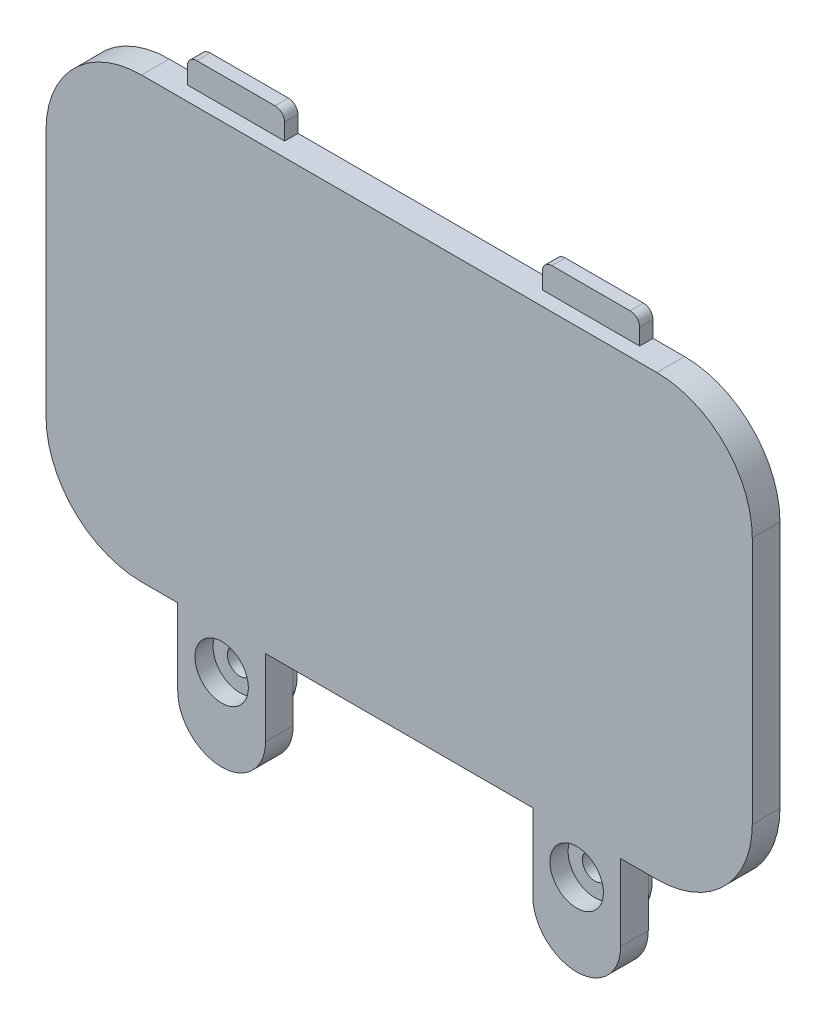
SolidWorks part; units mm, degrees
ref_plane "Plan de face" through (0, 0, 0) normal (0, 0, 1) x (1, 0, 0)
ref_plane "Plan de dessus" through (0, 0, 0) normal (0, 1, 0) x (1, 0, 0)
ref_plane "Plan de droite" through (0, 0, 0) normal (1, 0, 0) x (0, 0, -1)
sketch "Esquisse1" plane through (0, 0, 0) normal (0, 0, 1) x (1, 0, 0)
  line L3 (-14, -15.0013) -> (14, -15.0013) construction
  line L4 (23.2, -15.0013) -> (27, -15.0013) construction
  line L5 (37, -5.0013) -> (37, 20.9987) construction
  line L6 (27, 30.9987) -> (-27, 30.9987) construction
  line L7 (-37, 20.9987) -> (-37, -5.0013) construction
  line L8 (-27, -15.0013) -> (-23.2, -15.0013) construction
  line L10 (23.2, -23.0013) -> (23.2, -15.0013)
  line L11 (14, -15.0013) -> (14, -23.0013)
  line L12 (-14, -23.0013) -> (-14, -15.0013)
  line L13 (-14, -15.0013) -> (14, -15.0013)
  line L14 (23.2, -15.0013) -> (27, -15.0013)
  line L15 (37, -5.0013) -> (37, 20.9987)
  line L16 (27, 30.9987) -> (-27, 30.9987)
  line L17 (-37, 20.9987) -> (-37, -5.0013)
  line L18 (-27, -15.0013) -> (-23.2, -15.0013)
  line L19 (-23.2, -15.0013) -> (-23.2, -23.0013)
  arc A1 (27, -15.0013) -> (37, -5.0013) centre (27, -5.0013) ccw construction
  arc A2 (37, 20.9987) -> (27, 30.9987) centre (27, 20.9987) ccw construction
  arc A3 (-27, 30.9987) -> (-37, 20.9987) centre (-27, 20.9987) ccw construction
  arc A4 (-37, -5.0013) -> (-27, -15.0013) centre (-27, -5.0013) ccw construction
  arc A6 (14, -23.0013) -> (23.2, -23.0013) centre (18.6, -23.0013) ccw
  arc A7 (27, -15.0013) -> (37, -5.0013) centre (27, -5.0013) ccw
  arc A8 (37, 20.9987) -> (27, 30.9987) centre (27, 20.9987) ccw
  arc A9 (-27, 30.9987) -> (-37, 20.9987) centre (-27, 20.9987) ccw
  arc A10 (-37, -5.0013) -> (-27, -15.0013) centre (-27, -5.0013) ccw
  arc A11 (-23.2, -23.0013) -> (-14, -23.0013) centre (-18.6, -23.0013) ccw
  dimension "D2" = 4.6
  dimension "D3" = 4.6
  dimension "D1" = 8
extrude "Extrusion1" add sketch "Esquisse1" against normal blind 2.9
sketch "Esquisse2" plane through (0, 30.9987, 0) normal (0, 1, 0) x (-1, 0, 0)
  line L0 (-27, -2.9) -> (27, -2.9) construction
  line L1 (-23.7, -1.5) -> (-13.5, -1.5)
  line L2 (-23.7, -1.5) -> (-23.7, -2.9)
  line L3 (-23.7, -2.9) -> (-13.5, -2.9)
  line L4 (-13.5, -1.5) -> (-13.5, -2.9)
  line L6 (23.7, -1.5) -> (13.5, -1.5)
  line L7 (23.7, -1.5) -> (23.7, -2.9)
  line L8 (23.7, -2.9) -> (13.5, -2.9)
  line L9 (13.5, -1.5) -> (13.5, -2.9)
  dimension "D1" = 10.2
  dimension "D2" = 10.2
extrude "Extrusion2" add sketch "Esquisse2" along normal blind 2.7
fillet "Congé1" radius 1 4 edges at (-13.5, 33.6987, -2.2) (-23.7, 33.6987, -2.2) (13.5, 33.6987, -2.2) (23.7, 33.6987, -2.2)
sketch "Esquisse3" plane through (0, 0, -2.9) normal (0, 0, -1) x (-1, 0, 0)
  line L0 (35.6, -5.0013) -> (35.6, 0.7352)
  line L1 (23.2, -13.6013) -> (27, -13.6013)
  line L2 (21.8, -23.0013) -> (21.8, -13.6013)
  line L3 (15.4, -11.4648) -> (15.4, -23.0013)
  line L4 (-15.4, -11.4648) -> (-1.3334, -11.4648)
  line L5 (-15.4, -23.0013) -> (-15.4, -11.4648)
  line L6 (-21.8, -13.6013) -> (-21.8, -23.0013)
  line L7 (-27, -13.6013) -> (-23.2, -13.6013)
  line L8 (-35.6, 20.9987) -> (-35.6, 17.3987)
  line L9 (27, 29.5987) -> (23.2, 29.5987)
  line L10 (-23.2, 29.5987) -> (-23.2, 17.3987)
  line L11 (0.0666, -11.4648) -> (15.4, -11.4648)
  line L12 (-21.8, -13.6013) -> (-21.8, 0.7352)
  line L13 (-1.3334, 29.5987) -> (-1.3334, 17.3987)
  line L14 (0.0666, 29.5987) -> (0.0666, 17.3987)
  line L15 (21.8, -13.6013) -> (21.8, 0.7352)
  line L16 (23.2, 29.5987) -> (23.2, 17.3987)
  line L17 (-35.6, 17.3987) -> (-23.2, 17.3987)
  line L18 (-35.6, 15.9987) -> (-23.2, 15.9987)
  line L19 (-35.6, 2.1352) -> (-23.2, 2.1352)
  line L20 (-35.6, 0.7352) -> (-23.2, 0.7352)
  line L21 (-1.3334, 29.5987) -> (-21.8, 29.5987)
  line L22 (0.0666, 17.3987) -> (21.8, 17.3987)
  line L23 (-1.3334, 15.9987) -> (-1.3334, 2.1352)
  line L24 (0.0666, 15.9987) -> (0.0666, 2.1352)
  line L25 (0.0666, 15.9987) -> (21.8, 15.9987)
  line L26 (0.0666, 2.1352) -> (21.8, 2.1352)
  line L27 (0.0666, 0.7352) -> (21.8, 0.7352)
  line L28 (-1.3334, 0.7352) -> (-1.3334, -11.4648)
  line L29 (0.0666, 0.7352) -> (0.0666, -11.4648)
  line L30 (-21.8, 2.1352) -> (-21.8, 15.9987)
  line L31 (-21.8, 0.7352) -> (-1.3334, 0.7352)
  line L32 (-21.8, 2.1352) -> (-1.3334, 2.1352)
  line L33 (-23.2, 0.7352) -> (-23.2, -13.6013)
  line L34 (-23.2, 15.9987) -> (-23.2, 2.1352)
  line L35 (-21.8, 17.3987) -> (-1.3334, 17.3987)
  line L36 (-21.8, 15.9987) -> (-1.3334, 15.9987)
  line L37 (-21.8, 17.3987) -> (-21.8, 29.5987)
  line L38 (-35.6, 15.9987) -> (-35.6, 2.1352)
  line L39 (-23.2, 29.5987) -> (-27, 29.5987)
  line L40 (-35.6, 0.7352) -> (-35.6, -5.0013)
  line L41 (23.2, 2.1352) -> (35.6, 2.1352)
  line L42 (21.8, 2.1352) -> (21.8, 15.9987)
  line L43 (23.2, 0.7352) -> (23.2, -13.6013)
  line L44 (23.2, 0.7352) -> (35.6, 0.7352)
  line L45 (23.2, 17.3987) -> (35.6, 17.3987)
  line L46 (21.8, 17.3987) -> (21.8, 29.5987)
  line L47 (23.2, 15.9987) -> (35.6, 15.9987)
  line L48 (23.2, 15.9987) -> (23.2, 2.1352)
  line L49 (35.6, 17.3987) -> (35.6, 20.9987)
  line L50 (35.6, 2.1352) -> (35.6, 15.9987)
  line L51 (21.8, 29.5987) -> (0.0666, 29.5987)
  line L52 (-23.2, -23.0013) -> (-23.2, -15.0013) construction
  line L53 (23.2, -15.0013) -> (23.2, -23.0013) construction
  line L54 (14, -23.0013) -> (14, -15.0013) construction
  line L55 (-14, -15.0013) -> (-14, -23.0013) construction
  line L58 (-37, -5.0013) -> (-37, 20.9987) construction
  arc A0 (35.6, 20.9987) -> (27, 29.5987) centre (27, 20.9987) ccw
  arc A1 (27, -13.6013) -> (35.6, -5.0013) centre (27, -5.0013) ccw
  arc A2 (15.4, -23.0013) -> (21.8, -23.0013) centre (18.6, -23.0013) ccw
  arc A3 (-21.8, -23.0013) -> (-15.4, -23.0013) centre (-18.6, -23.0013) ccw
  arc A4 (-35.6, -5.0013) -> (-27, -13.6013) centre (-27, -5.0013) ccw
  arc A5 (-27, 29.5987) -> (-35.6, 20.9987) centre (-27, 20.9987) ccw
  arc A6 (-23.2, -23.0013) -> (-14, -23.0013) centre (-18.6, -23.0013) ccw construction
  arc A7 (14, -23.0013) -> (23.2, -23.0013) centre (18.6, -23.0013) ccw construction
  dimension "D10" = 1.4
  dimension "D11" = 1.4
  dimension "D1" = 1.4
  dimension "D2" = 1.4
  dimension "D3" = 1.4
  dimension "D4" = 1.4
  dimension "D5" = 1.4
  dimension "D6" = 1.4
  dimension "D7" = 1.4
  dimension "D8" = 1.4
  dimension "D9" = 1.4
  dimension "D12" = 12.2
  dimension "D13" = 12.2
  dimension "D14" = 1.4
extrude "Enlèv. mat.-Extru.1" cut sketch "Esquisse3" against normal blind 1
sketch "Esquisse4" plane through (0, 0, 0) normal (0, 0, 1) x (1, 0, 0)
  circle A0 centre (-18.6, -19.0013) radius 2.8
  circle A1 centre (18.6, -19.0013) radius 2.8
  dimension "D1" = 5.6
extrude "Enlèv. mat.-Extru.2" cut sketch "Esquisse4" against normal blind 2
sketch "Esquisse5" plane through (0, 0, -2.9) normal (0, 0, -1) x (-1, 0, 0)
  line L1 (-23.2, -23.0013) -> (-23.2, -15.0013) construction
  circle A0 centre (-18.6, -19.0013) radius 4.6
  circle A1 centre (18.6, -19.0013) radius 4.6
extrude "Extrusion3" add sketch "Esquisse5" along normal blind 1 and the other way blind 1
fillet "Congé2" radius 1 2 edges at (-23.2, -19.0013, -3.9) (14, -19.0013, -3.9)
sketch "Esquisse6" plane through (0, 0, -1.9) normal (0, 0, 1) x (1, 0, 0)
  circle A0 centre (18.6, -19.0013) radius 1.3
  circle A1 centre (-18.6, -19.0013) radius 1.3
  circle A2 centre (18.6, -19.0013) radius 2.8 construction
  circle A3 centre (-18.6, -19.0013) radius 2.8 construction
  dimension "D1" = 2.6
extrude "Enlèv. mat.-Extru.4" cut sketch "Esquisse6" against normal through all
sketch "Esquisse7" plane through (21.8, 0, 0) normal (-1, 0, 0) x (0, 0, 1)
  line L0 (-2.9, 32.6987) -> (-3.9, 32.3348)
  line L1 (-3.9, 32.3348) -> (-3.9, 29.5348)
  line L2 (-3.9, 29.5348) -> (-1.9, 27.3987)
  line L3 (-1.9, 29.5987) -> (-1.9, 20.9987) construction
  line L4 (-1.9, 27.3987) -> (-1.9, 29.5987)
  line L5 (-1.9, 29.5987) -> (-2.9, 29.5987)
  line L6 (-2.9, 29.5987) -> (-2.9, 32.6987)
  dimension "D1" = 1
  dimension "D2" = 2.8
  dimension "D3" = 2.2
  dimension "D4" = 70
extrude "Extrusion4" add sketch "Esquisse7" along normal blind 1
pattern_linear "Répétition linéaire1" count 2 spacing 6 along (-1, 0, 0) of "Extrusion4"
pattern_linear "Répétition linéaire2" count 2 spacing 36.6 along (-1, 0, 0) of "Extrusion4", "Répétition linéaire1"
